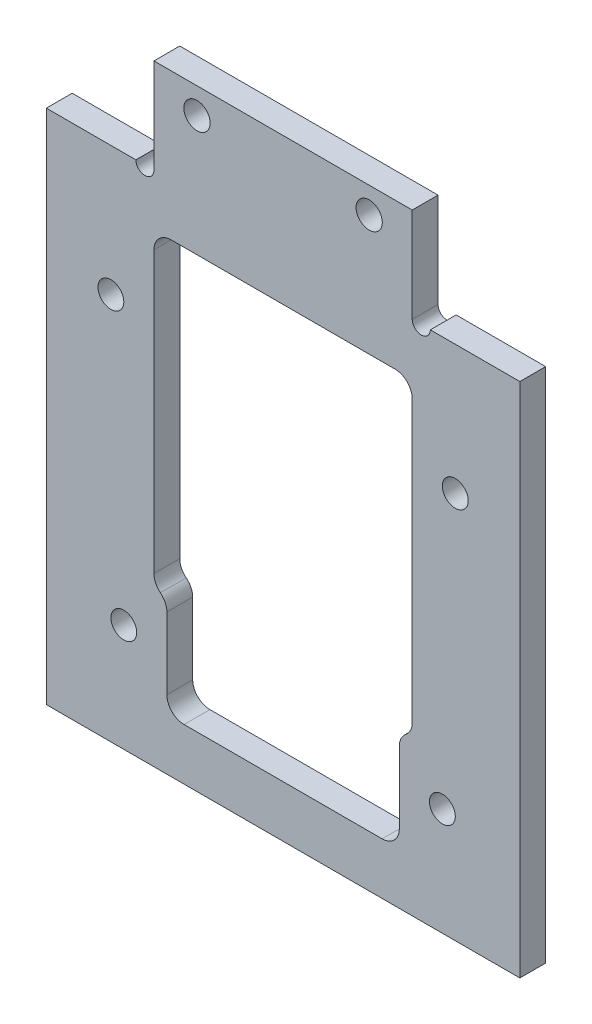
SolidWorks part; units mm, degrees
material "Thornel Mat VMA"
ref_plane "前视基准面" through (0, 0, 0) normal (0, 0, 1) x (1, 0, 0)
ref_plane "上视基准面" through (0, 0, 0) normal (0, 1, 0) x (1, 0, 0)
ref_plane "右视基准面" through (0, 0, 0) normal (1, 0, 0) x (0, 0, -1)
sketch "草图1" plane through (0, 0, 0) normal (0, 0, 1) x (1, 0, 0)
  line L1 (-27.5, -30) -> (27.5, -30)
  line L2 (-27.5, -30) -> (-27.5, 30)
  line L3 (-27.5, 30) -> (27.5, 30)
  line L4 (27.5, -30) -> (27.5, 30)
  line L5 (0, 30) -> (0, -30) construction
  line L6 (-27.5, 0) -> (27.5, 0) construction
  point P0 (0, 0)
  dimension "D1" = 55
  dimension "D2" = 60
extrude "凸台-拉伸1" add sketch "草图1" along normal blind 3
sketch "草图2" plane through (0, 0, 0) normal (0, 0, -1) x (-1, 0, 0)
  line L0 (-27.5, 30) -> (27.5, 30) construction
  line L1 (-15, 19) -> (15, 19)
  line L2 (-15, 19) -> (-15, 41)
  line L3 (-15, 41) -> (15, 41)
  line L4 (15, 19) -> (15, 41)
  line L5 (0, 41) -> (0, 19) construction
  line L6 (-15, 30) -> (15, 30) construction
  point P0 (0, 30)
  dimension "D1" = 30
  dimension "D2" = 11
extrude "凸台-拉伸2" add sketch "草图2" against normal up to surface (3 mm away) up to face at (0, 0, 3)
sketch "草图3" plane through (0, 0, 0) normal (0, 0, -1) x (-1, 0, 0)
  line L0 (-27.5, 30) -> (-15, 30) construction
  line L1 (15, 30) -> (27.5, 30) construction
  circle A0 centre (-16.05, 30) radius 1.05
  circle A1 centre (16.05, 30) radius 1.05
  dimension "D1" = 2.1
extrude "切除-拉伸1" cut sketch "草图3" against normal up to surface (3 mm away) up to face at (0, 17.75, 3)
sketch "草图4" plane through (0, 0, 3) normal (0, 0, 1) x (1, 0, 0)
  line L0 (-15, 38) -> (-10, 38) construction
  line L1 (-15, 41) -> (-15, 30) construction
  line L2 (-10, 38) -> (10, 38) construction
  line L3 (15, 41) -> (-15, 41) construction
  circle A0 centre (-10, 38) radius 1.525
  circle A1 centre (10, 38) radius 1.525
  dimension "D4" = 3.05
  dimension "D1" = 5
  dimension "D2" = 20
  dimension "D3" = 3
extrude "切除-拉伸2" cut sketch "草图4" against normal up to surface (3 mm away) up to face at (0, 19.99, 0)
sketch "草图5" plane through (0, 0, 0) normal (0, 0, -1) x (-1, 0, 0)
  line L0 (-27.5, -17.5) -> (27.5, -17.5) construction
  line L1 (-27.5, -30) -> (-27.5, 30) construction
  line L2 (27.5, 30) -> (27.5, -30) construction
  line L3 (0, 0) -> (0, -17.5) construction
  line L4 (27.5, -30) -> (-27.5, -30) construction
  circle A0 centre (-18.5, -17.5) radius 1.5
  circle A1 centre (18.5, -17.5) radius 1.5
  dimension "D2" = 3
  dimension "D1" = 12.5
  dimension "D3" = 37
extrude "切除-拉伸3" cut sketch "草图5" against normal blind 10
sketch "草图6" plane through (0, 0, 3) normal (0, 0, 1) x (1, 0, 0)
  circle A0 centre (20, 15) radius 1.5 construction
  circle A1 centre (-20, 15) radius 1.5 construction
  circle A2 centre (20, 15) radius 1.5
  circle A3 centre (-20, 15) radius 1.5
extrude "切除-拉伸4" cut sketch "草图6" against normal blind 10
sketch "草图7" plane through (0, 0, 3) normal (0, 0, 1) x (1, 0, 0)
  line L5 (-15, 24) -> (15, 24)
  line L6 (15, 24) -> (15, -12.5)
  line L10 (15, -12.5) -> (13.5, -12.5)
  line L11 (13.5, -12.5) -> (13.5, -24)
  line L12 (13.5, -24) -> (-13.5, -24)
  line L13 (-13.5, -24) -> (-13.5, -12.5)
  line L14 (-13.5, -12.5) -> (-15, -12.5)
  line L15 (-15, -12.5) -> (-15, 24)
  line L16 (27.5, 30) -> (17.1, 30) construction
  line L17 (-27.5, -30) -> (27.5, -30) construction
  circle A1 centre (20, 15) radius 1.5 construction
  circle A2 centre (-20, 15) radius 1.5 construction
  circle A3 centre (18.5, -17.5) radius 1.5 construction
  circle A4 centre (-18.5, -17.5) radius 1.5 construction
  dimension "D1" = 5
  dimension "D2" = 5
  dimension "D3" = 6
  dimension "D4" = 5
  dimension "D5" = 5
  dimension "D6" = 6
  dimension "D7" = 5
extrude "切除-拉伸5" cut sketch "草图7" against normal blind 10
fillet "圆角1" radius 2 6 edges at (-15, 24, 1.5) (15, 24, 1.5) (15, -12.5, 1.5) (-15, -12.5, 1.5) (-13.5, -24, 1.5) (13.5, -24, 1.5)
fillet "圆角2" radius 2 2 edges at (-13.5, -12.5, 1.5) (13.5, -12.5, 1.5)
